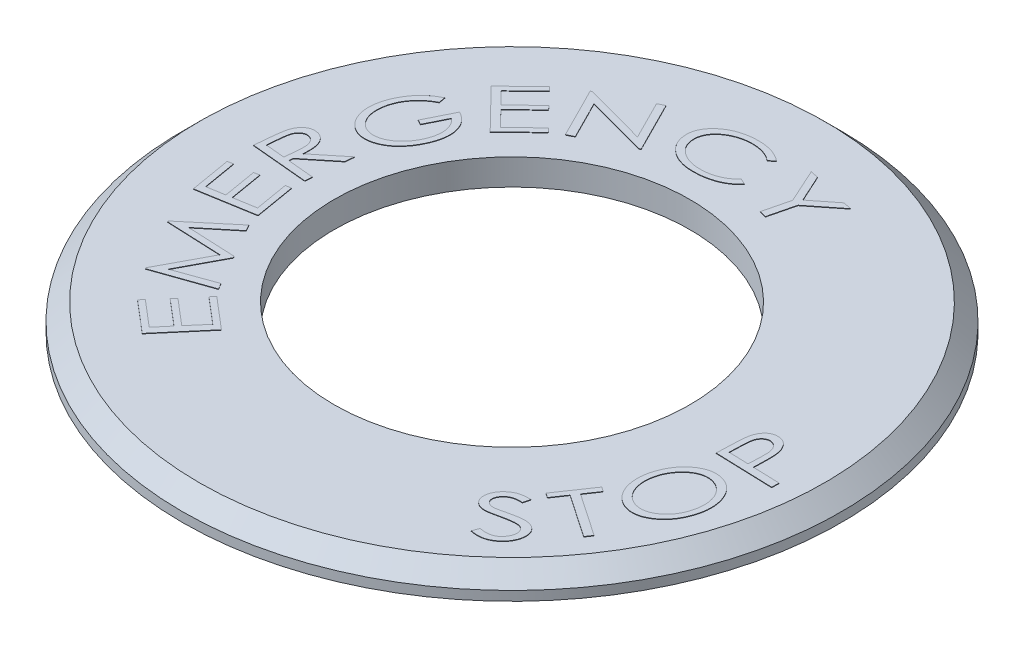
SolidWorks part; units mm, degrees
material "Plain Carbon Steel"
ref_plane "Front Plane" through (0, 0, 0) normal (0, 0, 1) x (1, 0, 0)
ref_plane "Top Plane" through (0, 0, 0) normal (0, 1, 0) x (1, 0, 0)
ref_plane "Right Plane" through (0, 0, 0) normal (1, 0, 0) x (0, 0, -1)
sketch "Sketch1" plane through (0, 0, 0) normal (0, 1, 0) x (1, 0, 0)
  circle A0 centre (0, 0) radius 20
  circle A1 centre (0, 0) radius 10.795
  dimension "D1" = 40
  dimension "D2" = 21.59
extrude "Extrude1" add sketch "Sketch1" along normal blind 1.5875
chamfer "Chamfer1" distance 1.016 angle 45 1 edges at (0, 1.5875, 20)
sketch "Sketch3" plane through (0, 0, 0) normal (0, -1, 0) x (1, 0, 0)
  line L0 (0, 20) -> (0, 19.238) construction
  line L1 (0, 19.238) -> (0, 13.97) construction
  line L2 (0, 13.97) -> (0, 0) construction
  line L3 (0, 0) -> (0, 10.033) construction
  line L4 (0, 10.033) -> (0, -13.97) construction
  line L5 (0, -13.97) -> (0, -29.083) construction
  line L6 (0, -29.083) -> (0, -29.845) construction
  line L7 (0.254, 19.2363) -> (0.254, 13.9677)
  line L8 (-0.254, 19.2363) -> (-0.254, 3.4654) construction
  line L9 (-0.254, 3.4654) -> (0, 3.4654) construction
  line L10 (0, 3.4654) -> (0.254, 3.4654) construction
  line L11 (18.071, 6.5985) -> (9.8454, 9.911)
  arc A0 (18.071, 6.5985) -> (-0.254, 19.2363) centre (0, 0) ccw
  arc A1 (9.8454, 9.911) -> (0.254, 13.9677) centre (0, 0) ccw
  circle A2 centre (0, 0) radius 10.795 construction
  circle A3 centre (0, 0) radius 20 construction
  dimension "D1" = 0.508
  dimension "D2" = 0.762
  dimension "D3" = 27.94
  dimension "D4" = 21.844
  dimension "D5" = 10.414
extrude "Extrude3" cut sketch "Sketch3" against normal blind 0.508 contours A1 L11 A0 L7 region at (8.3804, 0, 13.7395)
ref_axis "Axis1" through (0, 24.8873, 0) along (0, -1, 0)
pattern_circular "CirPattern1" count 8 over 360 about axis through (0, 24.8873, 0) along (0, -1, 0) of "Extrude3"
sketch "Sketch4" plane through (0, 0, 0) normal (0, -1, 0) x (1, 0, 0)
  circle A0 centre (0, 0) radius 11.557
  circle A1 centre (0, 0) radius 13.208
  arc A2 (-0.0464, 13.9699) -> (-9.697, 10.0563) centre (0, 0) ccw construction
  circle A3 centre (0, 0) radius 10.795 construction
  dimension "D1" = 0.762
  dimension "D2" = 0.762
extrude "Extrude4" cut sketch "Sketch4" against normal blind 0.508
sketch "Sketch5" plane through (0, 1.5875, 0) normal (0, 1, 0) x (1, 0, 0)
  circle A0 centre (0, 0) radius 17.78 construction
  circle A1 centre (0, 0) radius 12.7 construction
  text T0 "EMERGENCY         " font "Century Gothic" height in points 13
  text T1 "                                       STOP" font "Century Gothic" height 3.5
  dimension "D1" = 35.56
  dimension "D2" = 25.4
extrude "Extrude5" add sketch "Sketch5" along normal blind 0.0254
